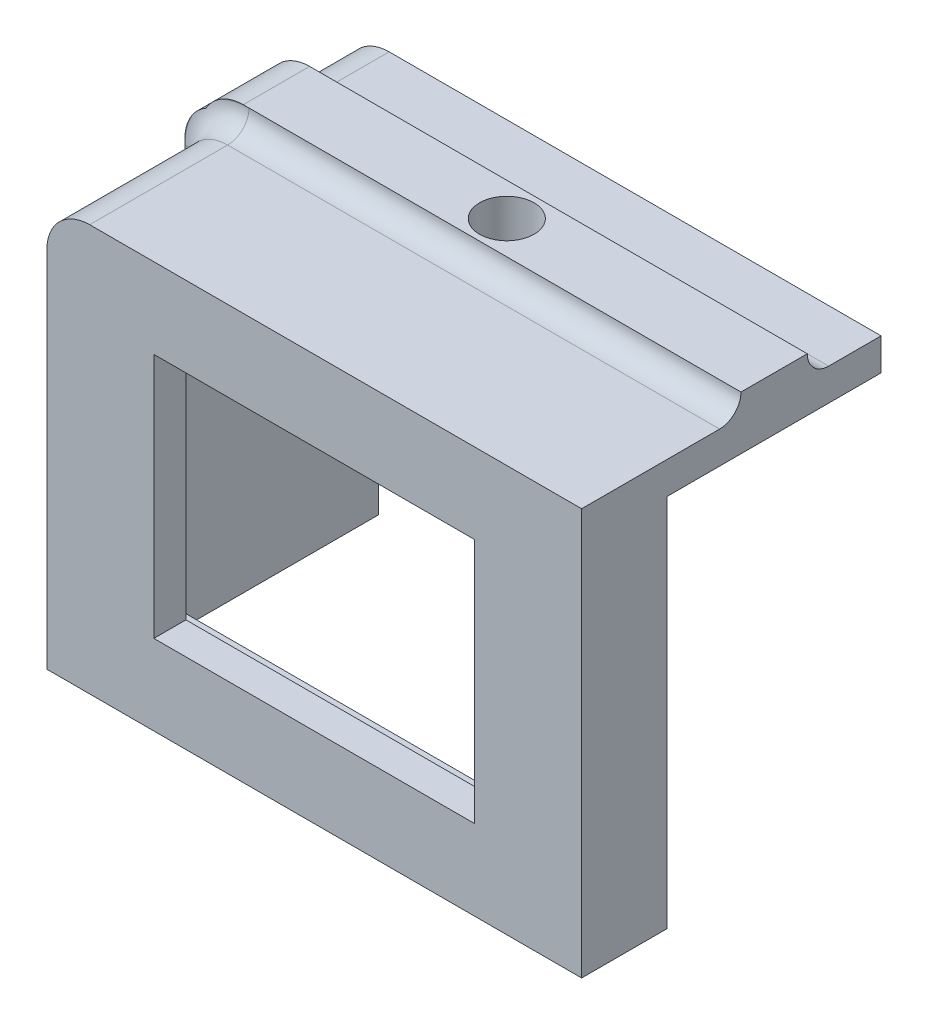
SolidWorks part; units mm, degrees
ref_plane "前视基准面" through (0, 0, 0) normal (0, 0, 1) x (1, 0, 0)
ref_plane "上视基准面" through (0, 0, 0) normal (0, 1, 0) x (1, 0, 0)
ref_plane "右视基准面" through (0, 0, 0) normal (1, 0, 0) x (0, 0, -1)
sketch "草图1" plane through (0, 0, 0) normal (0, 0, 1) x (1, 0, 0)
  line L0 (-22, 16) -> (25, 16)
  line L1 (-25, 19) -> (25, 19)
  line L2 (-25, 19) -> (-25, -19)
  line L3 (-25, -19) -> (25, -19)
  line L4 (25, 19) -> (25, -19)
  line L5 (0, -19) -> (0, 19) construction
  line L6 (-25, 0) -> (25, 0) construction
  line L7 (-15, 11.5) -> (15, 11.5)
  line L8 (-15, 11.5) -> (-15, -11.5)
  line L9 (-15, -11.5) -> (15, -11.5)
  line L10 (15, 11.5) -> (15, -11.5)
  line L11 (0, -11.5) -> (0, 11.5) construction
  line L12 (-15, 0) -> (15, 0) construction
  line L13 (-22, 16) -> (-22, -19)
  line L14 (-25, -16) -> (22, -16)
  line L15 (22, 19) -> (22, -16)
  point P0 (0, 0)
  point P4 (0, 0)
  dimension "D1" = 38
  dimension "D2" = 30
  dimension "D3" = 23
  dimension "D6" = 50
  dimension "D4" = 3
  dimension "D5" = 3
extrude "凸台-拉伸1" add sketch "草图1" against normal blind 3 contours L15 L0 L13 L14 L7 L10 L9 L8 region at (0, 15.4559, 0)
extrude "凸台-拉伸2" add sketch "草图1<3>" against normal blind 28 contours L15 L1 L2 L14 L13 L0 | L14 L2 L3 L13 | L1 L15 L0 L4 region at (-22.586, 0, 0) region at (23.5, 17.5, 0) region at (-23.5, -17.5, 0)
sketch "草图1<3>" plane through (0, 0, 0) normal (0, 0, 1) x (1, 0, 0) same geometry as "草图1"
extrude "凸台-拉伸3" add sketch "草图1<4>" against normal blind 8 contours L0 L15 L14 L13 L3 L4 region at (23.5, 15.414, 0)
sketch "草图1<4>" plane through (0, 0, 0) normal (0, 0, 1) x (1, 0, 0) same geometry as "草图1"
sketch "草图2" plane through (-25, 0, 0) normal (-1, 0, 0) x (0, 0, 1)
  line L0 (0, 19) -> (0, -19) construction
  line L3 (-28, 19) -> (0, 19) construction
  line L4 (-28, -19) -> (0, -19) construction
  line L5 (-21.1, 19) -> (-14.9, 19)
  line L6 (-21.1, 19) -> (-21.1, -19)
  line L7 (-21.1, -19) -> (-14.9, -19)
  line L8 (-14.9, 19) -> (-14.9, -19)
  line L9 (-18, -19) -> (-18, 19) construction
  line L10 (-21.1, 0) -> (-14.9, 0) construction
  circle A0 centre (-18, 0) radius 2.55
  dimension "D4" = 5.1
  dimension "D1" = 18
  dimension "D2" = 19
  dimension "D3" = 6.2
extrude "切除-拉伸2" cut sketch "草图2" against normal through all contours A0 region at (-25, 0, -18)
extrude "凸台-拉伸4" add sketch "草图2<3>" along normal blind 2
sketch "草图2<3>" plane through (-25, 0, 0) normal (-1, 0, 0) x (0, 0, 1) same geometry as "草图2"
sketch "草图3" plane through (0, 19, 0) normal (0, 1, 0) x (1, 0, 0)
  line L0 (-25, 0) -> (25, 0) construction
  line L1 (-25, 14.9) -> (-25, 0) construction
  line L2 (25, 21.1) -> (-25, 21.1)
  line L3 (25, 21.1) -> (25, 14.9)
  line L4 (25, 14.9) -> (-25, 14.9)
  line L5 (-25, 21.1) -> (-25, 14.9)
  line L6 (0, 14.9) -> (0, 21.1) construction
  line L7 (25, 18) -> (-25, 18) construction
  circle A0 centre (0, 18) radius 2.55
  dimension "D2" = 5.1
  dimension "D1" = 18
  dimension "D3" = 6.2
extrude "凸台-拉伸5" add sketch "草图3" along normal blind 2
extrude "切除-拉伸3" cut sketch "草图3<2>" against normal through all contours A0 region at (0, 19, -18)
sketch "草图3<2>" plane through (0, 19, 0) normal (0, 1, 0) x (1, 0, 0) same geometry as "草图3"
fillet "圆角2" radius 4 2 edges at (-25, 19, -7.45) (-25, 19, -24.55)
fillet "圆角3" radius 2 6 edges at (-25, -2, -14.9) (2, 19, -14.9) (-23.8284, 17.8284, -14.9) (2, 19, -21.1) (-23.8284, 17.8284, -21.1) (-25, -2, -21.1)
fillet "圆角4" radius 4 2 edges at (-25, 21, -18) (-27, 19, -18)
